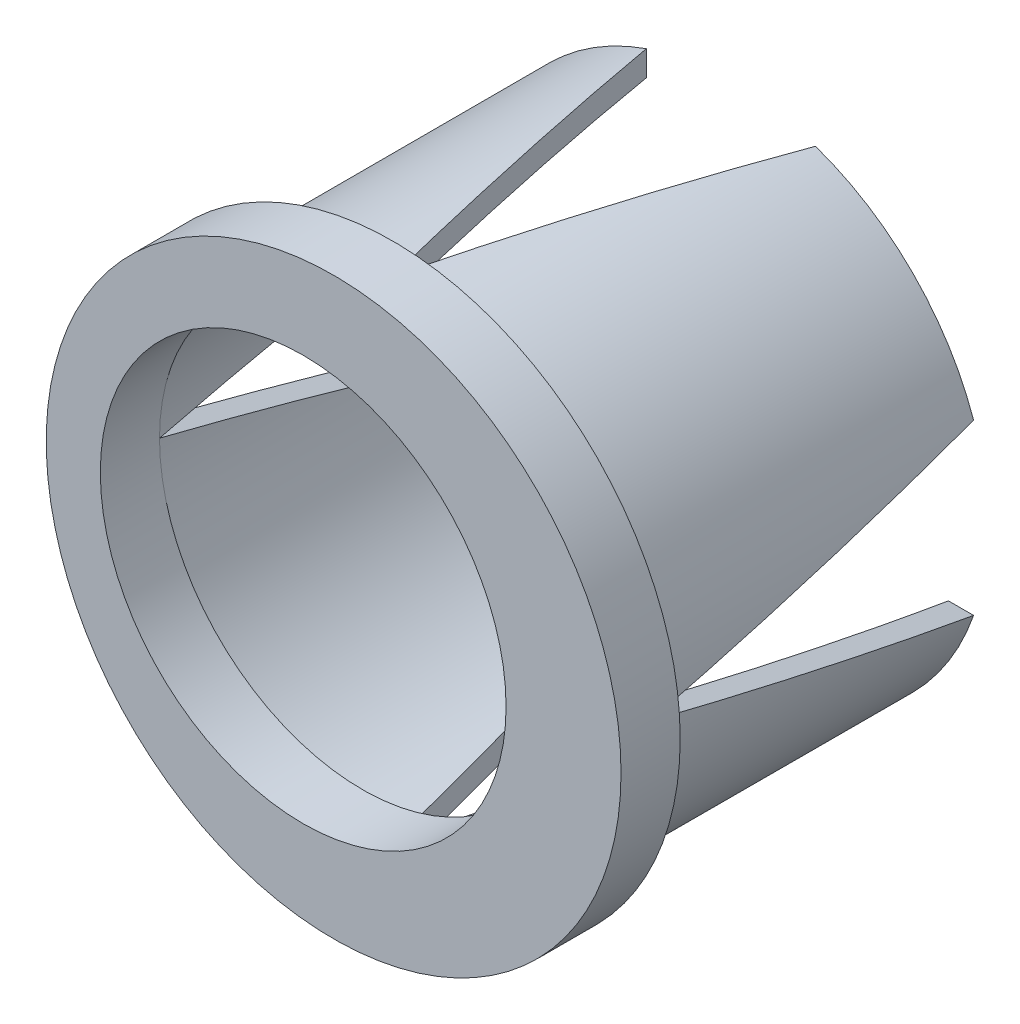
SolidWorks part; units mm, degrees
ref_plane "Front Plane" through (0, 0, 0) normal (0, 0, 1) x (1, 0, 0)
ref_plane "Top Plane" through (0, 0, 0) normal (0, 1, 0) x (1, 0, 0)
ref_plane "Right Plane" through (0, 0, 0) normal (1, 0, 0) x (0, 0, -1)
sketch "Sketch2" plane through (0, 0, 0) normal (0, 0, 1) x (1, 0, 0)
  line L0 (6.477, 0) -> (9.652, 0) construction
  line L1 (-8.763, 0) -> (-9.652, 0) construction
  circle A0 centre (0, 0) radius 9.652
  circle A1 centre (0, 0) radius 10.795
  circle A2 centre (-1.143, 0) radius 7.62
  circle A3 centre (0, 0) radius 8.763
  dimension "D1" = 19.304
  dimension "D2" = 21.59
  dimension "D3" = 15.24
  dimension "D4" = 3.175
  dimension "D5" = 0.889
extrude "Boss-Extrude1" add sketch "Sketch2" along normal blind 2.2225 contours A2 | A1 region at (-1.143, 0, 0)
extrude "Boss-Extrude2" add sketch "Sketch2<4>" against normal blind 12.7 contours A0 A3 region at (-9.379, 0, 0)
sketch "Sketch2<4>" plane through (0, 0, 0) normal (0, 0, 1) x (1, 0, 0) same geometry as "Sketch2"
sketch "Sketch3" plane through (0, 0, 0) normal (0, 1, 0) x (1, 0, 0)
  line L0 (0, 0) -> (3.175, 12.7)
  line L1 (0, 0) -> (-3.175, 12.7)
  line L2 (-3.175, 12.7) -> (3.175, 12.7)
  line L3 (0, 0) -> (0, 16.0568) construction
  point P4 (0, 12.7)
  dimension "D1" = 6.35
  dimension "D2" = 12.7
extrude "Cut-Extrude1" cut sketch "Sketch3" against normal blind 12.7 and the other way blind 12.7
sketch "Sketch5" plane through (0, 0, 0) normal (1, 0, 0) x (0, 0, -1)
  line L0 (0, 0) -> (12.7, 3.175)
  line L1 (12.7, 3.175) -> (12.7, -3.175)
  line L2 (12.7, -3.175) -> (0, 0)
  line L3 (0, 0) -> (20.1641, 0) construction
  point P4 (12.7, 0)
  dimension "D1" = 12.7
  dimension "D2" = 6.35
extrude "Cut-Extrude2" cut sketch "Sketch5" against normal blind 12.7 and the other way blind 12.7
